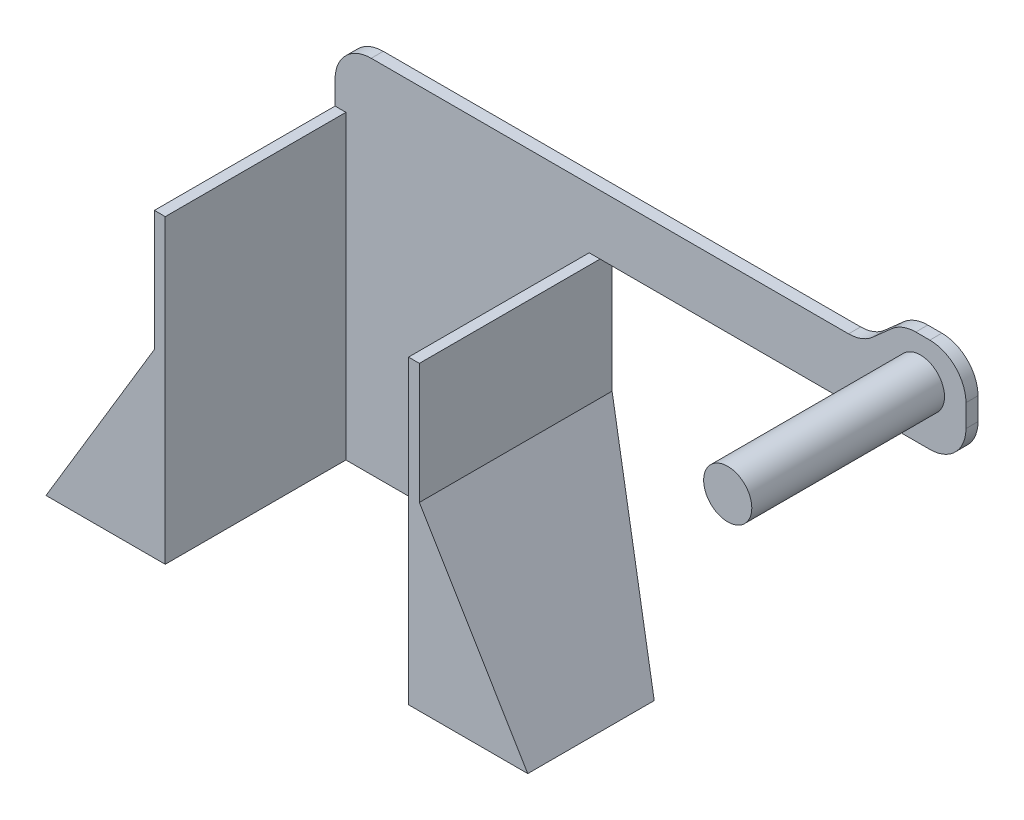
SolidWorks part; units mm, degrees
ref_plane "Front Plane" through (0, 0, 0) normal (0, 0, 1) x (1, 0, 0)
ref_plane "Top Plane" through (0, 0, 0) normal (0, 1, 0) x (1, 0, 0)
ref_plane "Right Plane" through (0, 0, 0) normal (1, 0, 0) x (0, 0, -1)
sketch "Sketch1" plane through (0, 0, 0) normal (0, 0, 1) x (1, 0, 0)
  line L1 (-11, -12.5) -> (11, -12.5)
  line L2 (-11, -12.5) -> (-11, 12.5)
  line L3 (-11, 12.5) -> (11, 12.5)
  line L4 (11, -12.5) -> (11, 12.5)
  line L5 (-11, -12.5) -> (11, 12.5) construction
  line L6 (-11, 12.5) -> (11, -12.5) construction
  point P0 (0, 0)
  dimension "D1" = 22
  dimension "D2" = 25
extrude "Boss-Extrude1" add sketch "Sketch1" along normal blind 16
sketch "Sketch2" plane through (0, 12.5, 0) normal (0, 1, 0) x (1, 0, 0)
  line L0 (-11, -8) -> (11, -8) construction
  line L1 (-11, -16) -> (-11, 0) construction
  line L2 (11, -16) -> (11, 0) construction
  line L3 (0, 0) -> (0, -16) construction
  line L4 (11, -16) -> (-11, -16) construction
  line L5 (11, 0) -> (-11, 0) construction
  line L10 (-10.1, 0) -> (10.1, 0)
  line L11 (-10.1, 0) -> (-10.1, -15)
  line L12 (-10.1, -15) -> (10.1, -15)
  line L13 (10.1, 0) -> (10.1, -15)
  point P11 (0, -8)
  point P18 (0, 0)
  dimension "D1" = 20.2
  dimension "D3" = 1
extrude "Cut-Extrude1" cut sketch "Sketch2" against normal through all
sketch "Sketch3" plane through (0, 0, 16) normal (0, 0, 1) x (1, 0, 0)
  line L0 (-11, -12.5) -> (-20, -12.5)
  line L1 (-20, -12.5) -> (-11, 2.5)
  line L2 (-11, 12.5) -> (-11, -12.5) construction
  line L3 (-11, 2.5) -> (-11, -12.5)
  line L4 (11, -12.5) -> (20, -12.5)
  line L5 (20, -12.5) -> (11, 2.5)
  line L6 (11, -12.5) -> (11, 12.5) construction
  line L7 (11, 2.5) -> (11, -12.5)
  dimension "D1" = 15
  dimension "D2" = 9
  dimension "D3" = 15
  dimension "D4" = 9
extrude "Boss-Extrude2" add sketch "Sketch3" against normal up to surface (16 mm away) up to face at (-10.55, 0, 0)
sketch "Sketch5" plane through (0, -12.5, 0) normal (0, -1, 0) x (1, 0, 0)
  line L3 (-15.05, 0) -> (-15.05, 16) construction
  line L4 (-20, 0) -> (-10.1, 0) construction
  line L5 (-20, 16) -> (20, 16) construction
  line L6 (15.05, 0) -> (15.05, 16) construction
  line L7 (10.1, 0) -> (20, 0) construction
  circle A0 centre (-15.05, 7.5) radius 1.5
  circle A1 centre (15.05, 7.5) radius 1.5
  dimension "D1" = 3
  dimension "D2" = 7.5
extrude "Cut-Extrude5" cut sketch "Sketch5" against normal blind 5.5
sketch "Sketch4" plane through (0, 0, 0) normal (0, 1, 0) x (1, 0, 0)
  line L14 (11, -16) -> (20, -10.5)
  line L15 (20, 0) -> (20, -16) construction
  line L16 (20, -10.5) -> (20, -16)
  line L17 (20, -16) -> (11, -16)
  line L27 (-11, -16) -> (-20, -16)
  line L32 (-20, -16) -> (-20, -10.5)
  line L33 (-20, 0) -> (-20, -16) construction
  line L34 (-20, -10.5) -> (-11, -16)
  dimension "D1" = 5.5
  dimension "D2" = 5.5
extrude "Cut-Extrude4" cut sketch "Sketch4" against normal through all both and the other way through all
sketch "Sketch6" plane through (0, 0, 16) normal (0, 0, 1) x (1, 0, 0)
  line L0 (11, 12.5) -> (41.3807, 12.5)
  line L1 (41.3807, 12.5) -> (41.3807, 20.3617)
  line L2 (41.3807, 20.3617) -> (36.0758, 20.3617)
  line L3 (36.0758, 20.3617) -> (32.7729, 17.4379)
  line L4 (32.7729, 17.4379) -> (-11, 17.4379)
  line L6 (-11, 12.5) -> (-11, 17.4379)
  line L13 (-11, -12.5) -> (11, -12.5)
  line L14 (11, -12.5) -> (11, 2.5)
  line L15 (11, 2.5) -> (11, 12.5)
  line L16 (11, 12.5) -> (-11, 12.5)
  line L17 (-11, 12.5) -> (-11, 2.5)
  line L18 (-11, 2.5) -> (-11, -12.5)
  line L22 (11, 12.5) -> (-11, 12.5)
  dimension "D1" = 0
extrude "Boss-Extrude3" add sketch "Sketch6" against normal blind 1
sketch "Sketch7" plane through (0, 0, 15) normal (0, 0, -1) x (-1, 0, 0)
  circle A0 centre (-37.6, 16.9) radius 2
  dimension "D1" = 4
extrude "Boss-Extrude4" add sketch "Sketch7" along normal blind 16
fillet "Fillet1" radius 3 5 edges at (-11, 17.4379, 15.5) (41.3807, 12.5, 15.5) (41.3807, 20.3617, 15.5) (36.0758, 20.3617, 15.5) (32.7729, 17.4379, 15.5)
chamfer "Chamfer1" distance 1 angle 45 2 edges at (15.05, -12.5, 6) (-15.05, -12.5, 6)
mirror "Mirror1" about plane through (0, 0, 0) normal (0, 0, 1) of bodies 114
delete or keep bodies "Body-Delete/Keep 1" type delete bodies bodies 114
